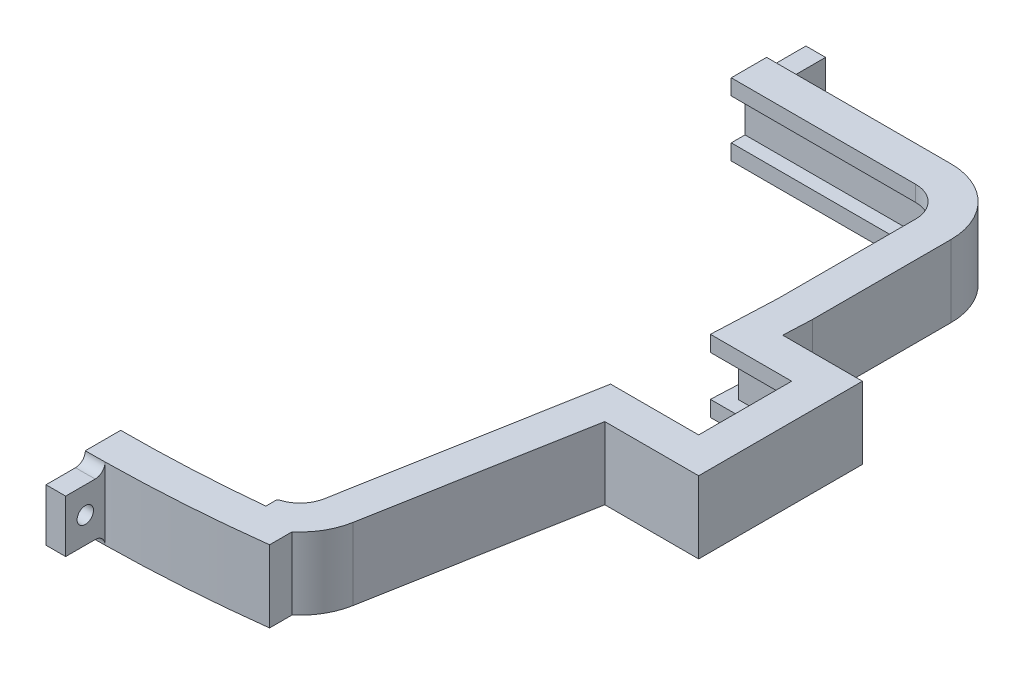
SolidWorks part; units mm, degrees
ref_plane "Front Plane" through (0, 0, 0) normal (0, 0, 1) x (1, 0, 0)
ref_plane "Top Plane" through (0, 0, 0) normal (0, 1, 0) x (1, 0, 0)
ref_plane "Right Plane" through (0, 0, 0) normal (1, 0, 0) x (0, 0, -1)
sketch "Sketch2" plane through (0, 0, 0) normal (0, 1, 0) x (1, 0, 0)
  line L6 (-32.15, 40) -> (-32.15, 19)
  line L8 (-28.15, 44) -> (28.15, 44)
  line L10 (32.15, 40) -> (32.15, 19)
  line L11 (-32.15, 19) -> (-31.6916, 8.5)
  line L12 (-28.15, 50) -> (28.15, 50)
  line L13 (38.15, 40) -> (38.15, 18.8691)
  line L14 (37.9592, 14.5) -> (38.15, 18.8691)
  line L15 (37.9592, 14.5) -> (50.124, 14.5)
  line L16 (50.124, -10.5) -> (50.124, 14.5)
  line L17 (35.7934, -10.5) -> (50.124, -10.5)
  line L18 (35.7934, -10.5) -> (29.9042, -43.0677)
  line L19 (26.5, -52.373) -> (26.5, -48.9417)
  line L20 (-26.5, -52.373) -> (-26.5, -48.9417)
  line L21 (-29.9042, -43.0677) -> (-35.7934, -10.5)
  line L22 (-50.124, -10.5) -> (-35.7934, -10.5)
  line L23 (-50.124, -10.5) -> (-50.124, 14.5)
  line L24 (-50.124, 14.5) -> (-37.9592, 14.5)
  line L30 (-38.15, 18.8691) -> (-37.9592, 14.5)
  line L31 (-38.15, 40) -> (-38.15, 18.8691)
  line L35 (-28.15, 46.7) -> (28.15, 46.7)
  line L36 (-50, 2) -> (50, 2) construction
  line L39 (-44.124, -4.5) -> (-30.7811, -4.5)
  line L40 (30.7811, -4.5) -> (44.124, -4.5)
  line L41 (31.6916, 8.5) -> (44.124, 8.5)
  line L42 (44.124, -4.5) -> (44.124, 8.5)
  line L43 (34.85, 40) -> (34.85, 18.9411)
  line L44 (-20.5, -47) -> (-20.5, -46.0775)
  line L45 (-44.124, -4.5) -> (-44.124, 8.5)
  line L46 (-44.124, 8.5) -> (-31.6916, 8.5)
  line L47 (-20.5, -47) -> (20.5, -47) construction
  line L48 (34.512, 11.2) -> (34.85, 18.9411)
  line L49 (31.6916, 8.5) -> (32.15, 19)
  line L50 (34.512, 11.2) -> (46.824, 11.2)
  line L51 (46.824, -7.2) -> (46.824, 11.2)
  line L52 (33.0366, -7.2) -> (46.824, -7.2)
  line L53 (33.0366, -7.2) -> (26.6569, -42.4804)
  line L54 (23.2, -49.4347) -> (23.2, -47.2089)
  line L55 (-23.2, -49.4347) -> (-23.2, -47.2089)
  line L56 (-26.6569, -42.4804) -> (-33.0366, -7.2)
  line L57 (-46.824, -7.2) -> (-33.0366, -7.2)
  line L58 (-46.824, -7.2) -> (-46.824, 11.2)
  line L59 (-46.824, 11.2) -> (-34.512, 11.2)
  line L60 (-34.85, 18.9411) -> (-34.512, 11.2)
  line L61 (-34.85, 40) -> (-34.85, 18.9411)
  line L62 (-21.5547, -45) -> (21.5547, -45) construction
  line L63 (-24, -42) -> (24, -42) construction
  line L64 (30.7811, -4.5) -> (24, -42)
  line L65 (-24, -42) -> (-30.7811, -4.5)
  line L66 (20.5, -47) -> (20.5, -46.0775)
  line L67 (-32.75, 40) -> (-32.75, 18.9869)
  line L68 (-32.75, 18.9869) -> (-32.3183, 9.1)
  line L69 (-44.724, 9.1) -> (-32.3183, 9.1)
  line L70 (-44.724, -5.1) -> (-44.724, 9.1)
  line L71 (-44.724, -5.1) -> (-31.2823, -5.1)
  line L72 (-24.5904, -42.1068) -> (-31.2823, -5.1)
  line L73 (-21.1, -47.5435) -> (-21.1, -46.0775)
  line L74 (21.1, -47.5435) -> (21.1, -46.0775)
  line L75 (31.2823, -5.1) -> (24.5904, -42.1068)
  line L76 (31.2823, -5.1) -> (44.724, -5.1)
  line L77 (44.724, -5.1) -> (44.724, 9.1)
  line L78 (32.3183, 9.1) -> (44.724, 9.1)
  line L79 (32.3183, 9.1) -> (32.75, 18.9869)
  line L80 (32.75, 40) -> (32.75, 18.9869)
  line L81 (-28.15, 44.6) -> (28.15, 44.6)
  arc A10 (-28.15, 44) -> (-32.15, 40) centre (-28.15, 40) ccw
  arc A11 (32.15, 40) -> (28.15, 44) centre (28.15, 40) ccw
  arc A12 (38.15, 40) -> (28.15, 50) centre (28.15, 40) ccw
  arc A13 (29.9042, -43.0677) -> (26.5, -48.9417) centre (20.0638, -41.2882) cw
  arc A14 (26.5, -48.9417) -> (26.5, -48.9417) centre (26.5, -48.9417) cw
  arc A15 (-26.5, -52.373) -> (26.5, -52.373) centre (0, 162.625) ccw
  arc A16 (-26.5, -48.9417) -> (-26.5, -48.9417) centre (-26.5, -48.9417) ccw
  arc A17 (-29.9042, -43.0677) -> (-26.5, -48.9417) centre (-20.0638, -41.2882) ccw
  arc A18 (-28.15, 50) -> (-38.15, 40) centre (-28.15, 40) ccw
  arc A19 (34.85, 40) -> (28.15, 46.7) centre (28.15, 40) ccw
  arc A20 (-20.5, -47) -> (20.5, -47) centre (0, 162.625) ccw
  arc A21 (-20.5, -46.0775) -> (-21.2128, -45.1197) centre (-21.5, -46.0775) ccw
  arc A22 (-24, -42) -> (-21.2128, -45.1197) centre (-20.0638, -41.2882) ccw
  arc A23 (24, -42) -> (21.2128, -45.1197) centre (20.0638, -41.2882) cw
  arc A24 (20.5, -46.0775) -> (21.2128, -45.1197) centre (21.5, -46.0775) cw
  arc A25 (26.6569, -42.4804) -> (23.2, -47.2089) centre (20.0638, -41.2882) cw
  arc A26 (23.2, -47.2089) -> (23.2, -47.2089) centre (23.2, -47.2089) cw
  arc A27 (-23.2, -49.4347) -> (23.2, -49.4347) centre (0, 162.625) ccw
  arc A28 (-23.2, -47.2089) -> (-23.2, -47.2089) centre (-23.2, -47.2089) ccw
  arc A29 (-26.6569, -42.4804) -> (-23.2, -47.2089) centre (-20.0638, -41.2882) ccw
  arc A30 (-28.15, 46.7) -> (-34.85, 40) centre (-28.15, 40) ccw
  arc A31 (-24.5904, -42.1068) -> (-21.3851, -45.6944) centre (-20.0638, -41.2882) ccw
  arc A32 (-21.1, -46.0775) -> (-21.3851, -45.6944) centre (-21.5, -46.0775) ccw
  arc A33 (-21.1, -47.5435) -> (21.1, -47.5435) centre (0, 162.625) ccw
  arc A34 (21.1, -46.0775) -> (21.3851, -45.6944) centre (21.5, -46.0775) cw
  arc A35 (24.5904, -42.1068) -> (21.3851, -45.6944) centre (20.0638, -41.2882) cw
  arc A36 (32.75, 40) -> (28.15, 44.6) centre (28.15, 40) ccw
  arc A37 (-28.15, 44.6) -> (-32.75, 40) centre (-28.15, 40) ccw
  point P0 (0, 0)
  point P1 (-29.7948, -34.9429)
  point P3 (29.7948, -34.9429)
  point P5 (32.15, 19)
  point P9 (-32.15, 19)
  point P15 (0, -46)
  point P18 (0, 2)
  point P24 (0, -48)
  point P54 (0, 0)
  point P76 (0, -47)
  point P77 (0, -42)
  dimension "D6" = 21
  dimension "D7" = 21
  dimension "D8" = 56.3
  dimension "D9" = 42
  dimension "D12" = 13
  dimension "D18" = 2
  dimension "D19" = 4
  dimension "D20" = 1
  dimension "D25" = 0
  dimension "D5" = 4
  dimension "D17" = 8
  dimension "D1" = 44
  dimension "D2" = 177.5
  dimension "D3" = 32.15
  dimension "D4" = 32.15
  dimension "D10" = 13
  dimension "D11" = 6.5
  dimension "D13" = 6.5
  dimension "D14" = 100
  dimension "D15" = 2
  dimension "D16" = 48
  dimension "D21" = 3
  dimension "D22" = 3
  dimension "D23" = 3.1197
  dimension "D24" = 0.9225
  dimension "D26" = 177.5
  dimension "D27" = 12.4324
  dimension "D28" = 12.4324
  dimension "D29" = 100.25
  dimension "D30" = 100.25
  dimension "D31" = 42
  dimension "D32" = 6
  dimension "D33" = 2.7
  dimension "D34" = 0.6
extrude "Boss-Extrude1" add sketch "Sketch2" against normal blind 4.5 contours L12 A18 L31 L30 L24 L23 L22 L21 A17 L20 A15 L19 A13 L18 L17 L16 L15 L14 L13 A12 A30 L35 A19 L43 L48 L50 L51 L52 L53 A25 L54 A27 L55 A29 L56 L57 L58 L59 L60 L61 | L35 A30 L61 L60 L59 L58 L57 L56 A29 L55 A27 L54 A25 L53 L52 L51 L50 L48 L43 A19 A37 L81 A36 L80 L79 L78 L77 L76 L75 A35 A34 L74 A33 L73 A32 A31 L72 L71 L70 L69 L68 L67 region at (0, 0, -48.5555) region at (0, 0, -45.3488)
extrude "Cut-Extrude3" cut sketch "Sketch2<6>" against normal blind 2.1 contours A11 L30 L6 | L35 A30 L61 L60 L59 L58 L57 L56 A29 L55 A27 L54 A25 L53 L52 L51 L50 L48 L43 A19 A37 L81 A36 L80 L79 L78 L77 L76 L75 A35 A34 L74 A33 L73 A32 A31 L72 L71 L70 L69 L68 L67 region at (0, 0, -45.3488) region at (-31.3113, 0, -43.1613)
sketch "Sketch2<6>" plane through (0, 0, 0) normal (0, 1, 0) x (1, 0, 0) same geometry as "Sketch2"
extrude "Boss-Extrude3" add sketch "Sketch2<7>" along normal blind 6.5 contours L59 L58 L57 A28 L54 L52 A11 L30 | L35 A30 L61 L60 L59 L58 L57 L56 A29 L55 A27 L54 A25 L53 L52 L51 L50 L48 L43 A19 A37 L81 A36 L80 L79 L78 L77 L76 L75 A35 A34 L74 A33 L73 A32 A31 L72 L71 L70 L69 L68 L67 region at (0, 0, -48.5555) region at (0, 0, -45.3488)
sketch "Sketch2<7>" plane through (0, 0, 0) normal (0, 1, 0) x (1, 0, 0) same geometry as "Sketch2"
extrude "Cut-Extrude4" cut sketch "Sketch2<8>" along normal blind 4.1 contours A11 L30 L6 | L35 A30 L61 L60 L59 L58 L57 L56 A29 L55 A27 L54 A25 L53 L52 L51 L50 L48 L43 A19 A37 L81 A36 L80 L79 L78 L77 L76 L75 A35 A34 L74 A33 L73 A32 A31 L72 L71 L70 L69 L68 L67 region at (0, 0, -45.3488) region at (-31.3113, 0, -43.1613)
sketch "Sketch2<8>" plane through (0, 0, 0) normal (0, 1, 0) x (1, 0, 0) same geometry as "Sketch2"
sketch "Sketch4" plane through (0, 0, 0) normal (1, 0, 0) x (0, 0, -1)
  line L1 (50, -3) -> (56, -3)
  line L2 (50, -3) -> (50, 5)
  line L3 (50, 5) -> (56, 5)
  line L4 (56, -3) -> (56, 5)
  line L5 (50, -3) -> (56, 5) construction
  line L6 (50, 5) -> (56, -3) construction
  line L7 (-60, -3) -> (-54, -3)
  line L8 (-60, -3) -> (-60, 5)
  line L9 (-60, 5) -> (-54, 5)
  line L11 (-60, -3) -> (-54, 5) construction
  line L12 (-60, 5) -> (-54, -3) construction
  line L13 (-54, 5) -> (-52, 5)
  line L15 (-54, -3) -> (-52, -3)
  line L16 (-52, 5) -> (-52, -3)
  circle A0 centre (53, 1) radius 1.25
  circle A1 centre (-57, 1) radius 1.25
  point P0 (53, 1)
  point P7 (-57, 1)
  point P9 (50, 1)
  point P26 (-54, 1)
  dimension "D3" = 2.5
  dimension "D6" = 2.5
  dimension "D1" = 6
  dimension "D2" = 8
  dimension "D4" = 6
  dimension "D5" = 8
  dimension "D7" = 57
  dimension "D8" = 1
  dimension "D9" = 2
  dimension "D10" = 53
  dimension "D11" = 1
extrude "Boss-Extrude4" add sketch "Sketch4" along normal blind 3 and the other way blind 3 contours L16 L13 L9 L8 L7 L15 A1 | L1 L4 L3 L2 A0 region at (0, 1, -50.1) region at (0, 1, 59.8869)
fillet "Fillet1" radius 1.5 4 edges at (0, 5, 54) (0, -3, 54) (0, 5, -50) (0, -3, -50)
sketch "Sketch5" plane through (0, 0, 0) normal (1, 0, 0) x (0, 0, -1)
  line L1 (-75, -20) -> (75, -20)
  line L2 (-75, -20) -> (-75, 20)
  line L3 (-75, 20) -> (75, 20)
  line L4 (75, -20) -> (75, 20)
  line L5 (-75, -20) -> (75, 20) construction
  line L6 (-75, 20) -> (75, -20) construction
  point P0 (0, 0)
extrude "Cut-Extrude5" cut sketch "Sketch5" against normal through all
